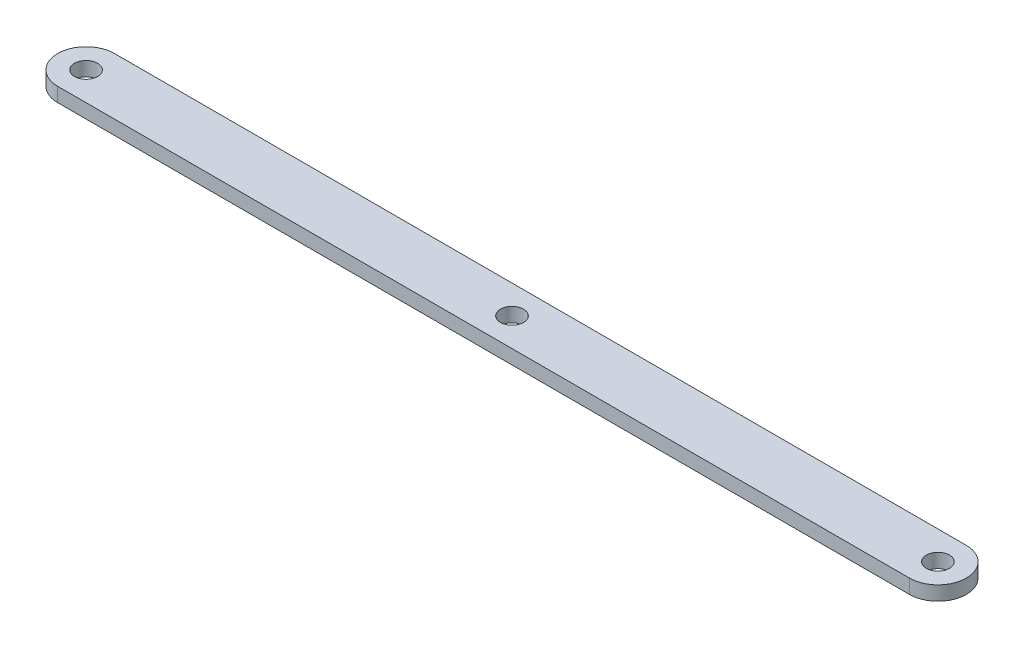
SolidWorks part; units mm, degrees
ref_plane "Front Plane" through (0, 0, 0) normal (0, 0, 1) x (1, 0, 0)
ref_plane "Top Plane" through (0, 0, 0) normal (0, 1, 0) x (1, 0, 0)
ref_plane "Right Plane" through (0, 0, 0) normal (1, 0, 0) x (0, 0, -1)
sketch "Sketch1" plane through (0, 0, 0) normal (0, 1, 0) x (1, 0, 0)
  line L0 (-95.25, 0) -> (95.25, 0) construction
  line L1 (-95.25, 6.35) -> (95.25, 6.35)
  line L2 (-95.25, -6.35) -> (95.25, -6.35)
  arc A0 (-95.25, 6.35) -> (-95.25, -6.35) centre (-95.25, 0) ccw
  arc A1 (95.25, -6.35) -> (95.25, 6.35) centre (95.25, 0) ccw
  circle A2 centre (95.25, 0) radius 2.5797
  circle A3 centre (-95.25, 0) radius 2.5797
  circle A4 centre (0, 0) radius 2.5797
  point P3 (0, 0)
  dimension "D2" = 6.35
  dimension "D3" = 5.1594
  dimension "D1" = 190.5
extrude "Boss-Extrude1" add sketch "Sketch1" along normal blind 3.175
